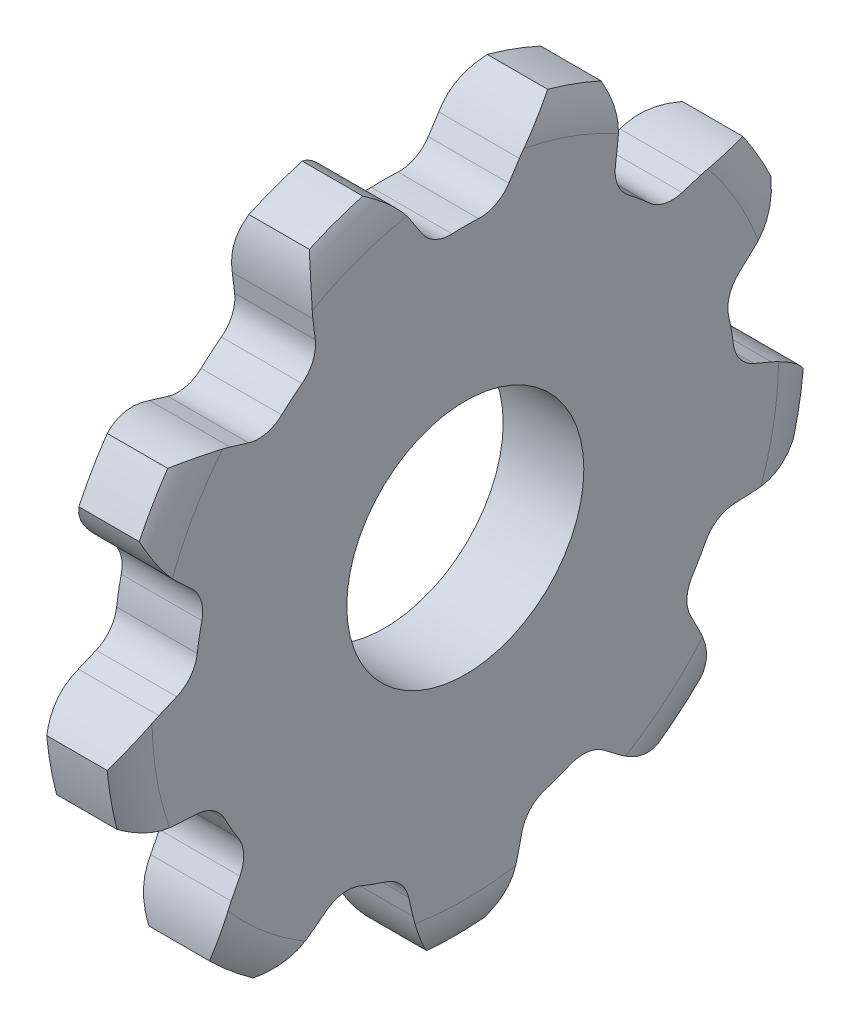
SolidWorks part; units mm, degrees
ref_plane "Plane1" through (0, 0, 0) normal (0, 0, 1) x (1, 0, 0)
ref_plane "Plane2" through (0, 0, 0) normal (0, 1, 0) x (1, 0, 0)
ref_plane "Plane3" through (0, 0, 0) normal (1, 0, 0) x (0, 0, -1)
sketch "Clipboard" plane through (0, 0, 0) normal (0, 1, 0) x (1, 0, 0)
  line L0 (0, 0) -> (22.6789, -3.592)
  line L1 (-15, 0) -> (100, 0) construction
  line L2 (0, 0) -> (-2.1039, 2.3779)
  line L3 (0, 0) -> (-11.863, 4.5341)
  line L4 (0, 0) -> (8.5297, 1.351)
  line L5 (0, 0) -> (-20.9428, -7.811)
  line L6 (0, 0) -> (-7.1589, -4.8301)
  line L7 (-2.1039, 2.3779) -> (2.7074, 24.206)
  line L8 (-76.2, 54.61) -> (-47.9044, 54.61)
  line L9 (-67.0794, 25.4907) -> (-62.6246, 26.5192)
  line L10 (-76.2, 71.12) -> (-42.6324, 71.12)
  circle A0 centre (0, 0) radius 7.9375
  circle A1 centre (0, 0) radius 25.4
  circle A2 centre (0, 0) radius 25.4
  dimension "Num_teeth" = 9
  dimension "Pitch_radius" = 33.5676
  dimension "H" = 4.572
  dimension "Thickness" = 8.636
sketch "BasProSke" plane through (0, 0, 0) normal (0, 1, 0) x (1, 0, 0)
  line L0 (-10, 0) -> (60, 0) construction
  line L1 (0, 0) -> (0, 33.5676)
  line L2 (0, 0) -> (8.636, 0)
  line L3 (8.636, 0) -> (8.636, 33.5676)
  line L4 (7.5565, 37.4538) -> (1.0795, 37.4538)
  arc A0 (0, 33.5676) -> (1.0795, 37.4538) centre (7.5349, 33.5676) cw
  arc A1 (8.636, 33.5676) -> (7.5565, 37.4538) centre (1.1011, 33.5676) ccw
  dimension "D1" = 7.5349
  dimension "Thickness" = 8.636
  dimension "Diameter" = 74.9076
revolve "Base-Revolve" add sketch "BasProSke" angle 360 about L0
sketch "TooCutSke" plane through (0, 0, 0) normal (1, 0, 0) x (0, 0, -1)
  line L0 (-4.6667, 30.5715) -> (-5.7922, 32.3047)
  line L1 (0, 0) -> (0, 107) construction
  line L2 (1.1481, 0) -> (1.1481, 288.74) construction
  line L3 (4.6667, 30.5715) -> (5.7922, 32.3047)
  line L5 (1.1481, 35.3206) -> (42.4634, 8.4901) construction
  arc A0 (1.4197, 28.9104) -> (-1.4197, 28.9104) centre (0, 0) ccw
  arc A1 (1.4197, 28.9104) -> (4.6667, 30.5715) centre (1.5991, 32.5636) ccw
  arc A2 (-1.4197, 28.9104) -> (-4.6667, 30.5715) centre (-1.5991, 32.5636) cw
  circle A3 centre (0, 0) radius 33.5676 construction
  circle A4 centre (1.1481, 33.548) radius 4.572 construction
  arc A5 (5.7922, 32.3047) -> (13.6084, 37.3886) centre (15.4208, 26.0518) cw
  arc A6 (-5.7922, 32.3047) -> (-13.6084, 37.3886) centre (-15.4208, 26.0518) ccw
  arc A7 (13.6084, 37.3886) -> (-13.6084, 37.3886) centre (0, 0) ccw
  dimension "Pitch_radius" = 33.5676
  dimension "R" = 3.6576
  dimension "Dr" = 28.9453
  dimension "H" = 4.572
  dimension "Ag" = 66
  dimension "L" = 2.0665
  dimension "Angle" = 40
extrude "ToothCut" cut sketch "TooCutSke" along normal through all
pattern_circular "TeethCuts" count 9 every 40 about axis through (-10, 0, 0) along (1, 0, 0) of "ToothCut"
sketch "HubNeaOneSke" plane through (0, 0, 0) normal (-1, 0, 0) x (0, 0, 1)
  circle A0 centre (0, 0) radius 25.4
  dimension "Diameter" = 50.8
extrude "HubNearOne" [suppressed] add sketch "HubNeaOneSke" along normal blind 13.7161
sketch "HubNeaBotSke" plane through (0, 0, 0) normal (-1, 0, 0) x (0, 0, 1)
  circle A0 centre (0, 0) radius 25.4
  dimension "Diameter" = 50.8
extrude "HubNearBoth" [suppressed] add sketch "HubNeaBotSke" along normal blind 6.858
ref_plane "FarPln" through (8.636, 0, 0) normal (1, 0, 0) x (0, 0, -1)
sketch "HubFarSke" plane through (8.636, 0, 0) normal (1, 0, 0) x (0, 0, -1)
  circle A0 centre (0, 0) radius 25.4
  dimension "Diameter" = 50.8
extrude "HubFar" [suppressed] add sketch "HubFarSke" along normal blind 6.858
sketch "BorSke" plane through (0, 0, 0) normal (1, 0, 0) x (0, 0, -1)
  circle A0 centre (0, 0) radius 12.7
  dimension "Diameter" = 25.4
extrude "Bore" cut sketch "BorSke" along normal mid plane 44.7041
sketch "KeySke" plane through (0, 0, 0) normal (1, 0, 0) x (0, 0, -1)
  line L0 (-3.175, 0) -> (-3.175, 15.5956)
  line L1 (-3.175, 15.5956) -> (3.175, 15.5956)
  line L2 (3.175, 15.5956) -> (3.175, 0)
  line L3 (0, 0) -> (0, 34) construction
  line L4 (-3.175, 0) -> (3.175, 0)
  dimension "Width" = 6.35
extrude "Keyway" [suppressed] cut sketch "KeySke" along normal mid plane 44.7041
pattern_circular "Keyway2" [suppressed] count 2 every 90 about axis through (-10, 0, 0) along (1, 0, 0) reverse direction yes
equation "\"Num_teeth@Clipboard\" = int( \"Num_teeth@Clipboard\" )"
equation "\"Num_teeth@Clipboard\" = ((sgn( \"Num_teeth@Clipboard\" - 5.0)+1)*( \"Num_teeth@Clipboard\" - 5.0))/2 +5.0"
equation "' \"Num_teeth@Clipboard\" = ((sgn( \"Num_teeth@Clipboard\" - 200.0)-1)*( \"Num_teeth@Clipboard\" - 200.0))/-2 +200.0"
equation "\"OAL@Clipboard\" = \"Thickness@Clipboard\""
equation "\"Pitch_radius@Clipboard\" = ( \"Pitch@Clipboard\" / 2.0) / sin(3.14159265 / \"Num_teeth@Clipboard\" )"
equation "\"MHD@Clipboard\" =2.0 * ( \"Pitch_radius@Clipboard\" * 0.9985 -  \"H@Clipboard\" )"
equation "\"MHD@Clipboard\" = ((sgn( \"MHD@Clipboard\" - \"Hub_dia@Clipboard\" )-1)*( \"MHD@Clipboard\" - \"Hub_dia@Clipboard\" ))/-2+ \"Hub_dia@Clipboard\""
equation "\"OAL@Clipboard\" = ((sgn( \"OAL@Clipboard\" - \"Overall_len@Clipboard\" )+1)*( \"OAL@Clipboard\" - \"Overall_len@Clipboard\" ))/2 + \"Overall_len@Clipboard\" + 0.000002"
equation "\"Num_teeth@TeethCuts\" = int( \"Show_teeth@Clipboard\" ) + 1"
equation "\"Num_teeth@TeethCuts\" = ((sgn( \"Num_teeth@TeethCuts\" - \"Num_teeth@Clipboard\" )-1)*( \"Num_teeth@TeethCuts\" - \"Num_teeth@Clipboard\" ))/-2+ \"Num_teeth@Clipboard\""
equation "\"Num_teeth@TeethCuts\" = ((sgn( \"Num_teeth@TeethCuts\" - 2.0)+1)*( \"Num_teeth@TeethCuts\" - 2.0))/2 +2.0"
equation "\"Angle@TeethCuts\" = 360.0 / \"Num_teeth@Clipboard\""
equation "\"Pitch_radius@TooCutSke\" = \"Pitch_radius@Clipboard\""
equation "\"Cp@TooCutSke\" = 0.05 * \"Pitch@Clipboard\""
equation "\"Rt@TooCutSke\" = 0.5 * \"Pitch@Clipboard\""
equation "\"R@TooCutSke\"  = 0.8 * \"H@Clipboard\""
equation "\"Dr@TooCutSke\" = \"Pitch_radius@Clipboard\" * 0.9985 -  \"H@Clipboard\""
equation "\"Ag@TooCutSke\" =  2.0 * \"Ap@Clipboard\" + 360.0 / \"Num_teeth@Clipboard\""
equation "\"L@TooCutSke\" = 0.01 * \"Pitch@Clipboard\" * \"Num_teeth@Clipboard\""
equation "\"H@TooCutSke\" = \"H@Clipboard\""
equation "\"Angle@TooCutSke\" =  360.0 / \"Num_teeth@Clipboard\""
equation "\"Diameter@BasProSke\" = 2.0 * \"Pitch_radius@Clipboard\"  + 1.7 * \"H@Clipboard\""
equation "\"Thickness@BasProSke\"  = \"Thickness@Clipboard\""
equation "\"G1@BasProSke\" =  \"Thickness@Clipboard\" * 0.125"
equation "\"G2@BasProSke\" =   \"Thickness@Clipboard\" * 0.125"
equation "\"H1@BasProSke\" =  \"Diameter@BasProSke\" / 2.0 - \"Pitch_radius@Clipboard\""
equation "\"H2@BasProSke\" =  \"Diameter@BasProSke\" / 2.0 - \"Pitch_radius@Clipboard\""
equation "\"Diameter@HubNeaOneSke\" = \"MHD@Clipboard\""
equation "\"Length@HubNearOne\" = \"OAL@Clipboard\" - \"Thickness@BasProSke\""
equation "\"Diameter@HubNeaBotSke\" = \"MHD@Clipboard\""
equation "\"Length@HubNearBoth\" = ( \"OAL@Clipboard\" - \"Thickness@BasProSke\" ) / 2.0"
equation "\"Thickness@FarPln\" = \"Thickness@BasProSke\""
equation "\"Diameter@HubFarSke\" = \"MHD@Clipboard\""
equation "\"Length@HubFar\" = ( \"OAL@Clipboard\" - \"Thickness@BasProSke\" ) / 2.0"
equation "\"D1@Bore\" = \"OAL@Clipboard\" * 2.0"
equation "\"D1@Keyway\" = \"OAL@Clipboard\" * 2.0"
equation "\"Offset@KeySke\" = \"T_dim@Clipboard\" - \"Diameter@BorSke\" / 2.0"
